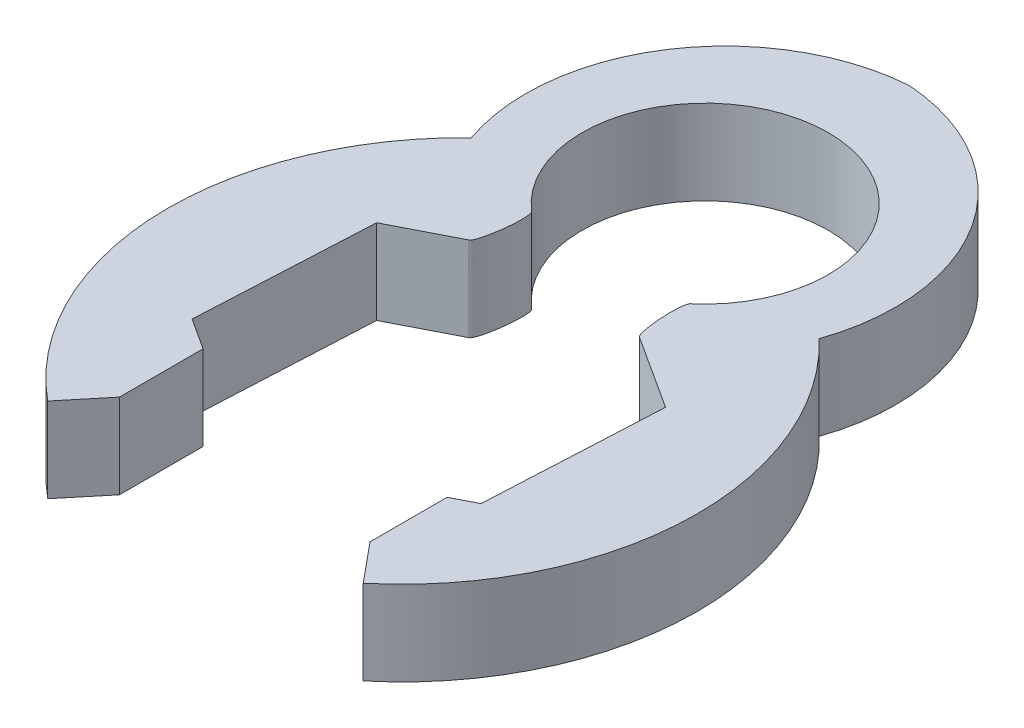
SolidWorks part; units mm, degrees
ref_plane "Front Plane" through (0, 0, 0) normal (0, 0, 1) x (1, 0, 0)
ref_plane "Top Plane" through (0, 0, 0) normal (0, 1, 0) x (1, 0, 0)
ref_plane "Right Plane" through (0, 0, 0) normal (1, 0, 0) x (0, 0, -1)
sketch "Sketch3" plane through (0, 0, 0) normal (0, 1, 0) x (1, 0, 0)
  line L0 (-7.2765, 0.1114) -> (11.8281, 0.1114) construction
  line L1 (-2.4796, 5.151) -> (-2.4796, 6.4742)
  line L2 (5.874, 3.0075) -> (0.3324, 6.5907)
  line L3 (0.3324, 6.5907) -> (-5.5415, 3.5833)
  line L4 (-5.5415, 3.5833) -> (-5.874, -3.0075)
  line L5 (-5.874, -3.0075) -> (-0.3324, -6.5907)
  line L6 (-0.3324, -6.5907) -> (5.5415, -3.5833)
  line L7 (5.5415, -3.5833) -> (5.874, 3.0075)
  line L8 (2.4796, 5.151) -> (2.4796, 6.4742)
  line L9 (-4.7012, -3.7658) -> (-4.7012, -6.9056)
  line L10 (-4.7012, -6.9056) -> (-5.9188, -8.3785)
  line L11 (0, 2.9063) -> (0, -1.8101) construction
  line L12 (4.7012, -6.9056) -> (5.9188, -8.3785)
  line L13 (4.7012, -3.7658) -> (4.7012, -6.9056)
  circle A0 centre (0, 0) radius 5.715 construction
  circle A1 centre (0, 10.3692) radius 4.6174
  arc A2 (-5.9188, -8.3785) -> (-6.5266, 8.121) centre (1.1246, 0.1419) cw
  arc A3 (-6.5266, 8.121) -> (0, 18.035) centre (0.5425, 10.5725) cw
  arc A4 (6.5266, 8.121) -> (0, 18.035) centre (-0.5425, 10.5725) ccw
  arc A5 (5.9188, -8.3785) -> (6.5266, 8.121) centre (-1.1246, 0.1419) ccw
  dimension "D1" = 11.43
  dimension "D2" = 0
extrude "Boss-Extrude1" add sketch "Sketch3" along normal blind 3.175 contours L12 A5 A4 A3 A2 L10 L9 L5 L4 L3 L1 A1 L8 L2 L7 L6 L13 | A1 L1 L3 | A1 L2 L8 region at (-4.1612, 0, -4.6613) region at (-2.0247, 0, -5.8096) region at (2.1055, 0, -5.8575)
fillet "Fillet6" radius 1.27 2 edges at (1.328, 1.5875, -5.947) (-1.0635, 1.5875, -5.876) conic radius 6.35
sketch "Sketch4" plane through (0, 3.175, 0) normal (0, 1, 0) x (1, 0, 0)
  line L1 (-6.1573, 3.9814) -> (-6.5266, -3.3416)
  line L2 (-6.5266, -3.3416) -> (-0.3694, -7.323)
  line L3 (-0.3694, -7.323) -> (6.1573, -3.9814)
  line L4 (6.1573, -3.9814) -> (6.5266, 3.3416)
  line L5 (6.5266, 3.3416) -> (0.3694, 7.323)
  line L6 (0.3694, 7.323) -> (-6.1573, 3.9814)
  circle A0 centre (0, 0) radius 6.35 construction
